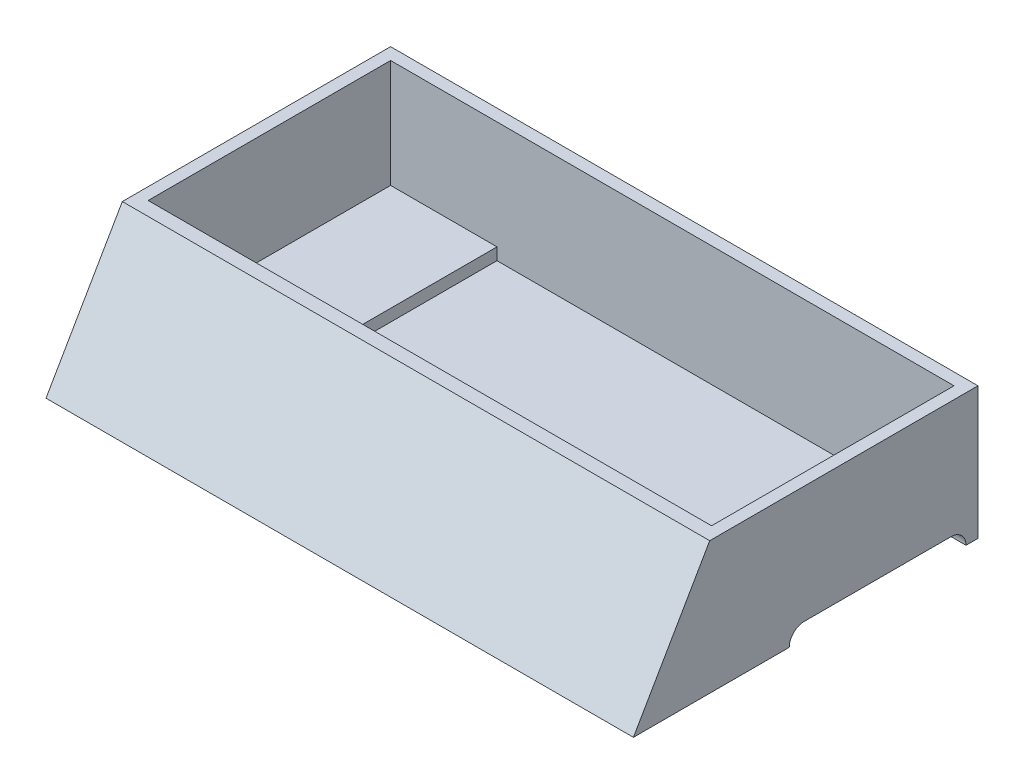
SolidWorks part; units mm, degrees
ref_plane "Alzado" through (0, 0, 0) normal (0, 0, 1) x (1, 0, 0)
ref_plane "Planta" through (0, 0, 0) normal (0, 1, 0) x (1, 0, 0)
ref_plane "Vista lateral" through (0, 0, 0) normal (1, 0, 0) x (0, 0, -1)
sketch "Croquis1" plane through (0, 0, 0) normal (1, 0, 0) x (0, 0, -1)
  line L0 (0, 0) -> (114.98, 0)
  line L1 (114.98, 0) -> (114.98, 44.1)
  line L2 (114.98, 44.1) -> (25.4611, 44.1)
  line L3 (0, 0) -> (25.4611, 44.1)
  line L4 (114.9845, -5.19) -> (114.9845, 15.0485) construction
  dimension "D1" = 114.98
  dimension "D2" = 44.1
  dimension "D3" = 120
extrude "Saliente-Extruir1" add sketch "Croquis1" along normal blind 196
shell "Vaciado1" thickness 4 removed face at (98, 44.1, -70.2206)
sketch "Croquis2" plane through (0, 0, 0) normal (0, -1, 0) x (-1, 0, 0)
  line L0 (-196, 114.98) -> (0, 114.98) construction
  line L1 (-37.5, 51.9947) -> (0, 51.9947)
  line L2 (-37.5, 51.9947) -> (-37.5, 110.98)
  line L3 (-37.5, 110.98) -> (0, 110.98)
  line L4 (0, 51.9947) -> (0, 110.98)
  line L5 (-37.5, 51.9947) -> (0, 110.98) construction
  line L6 (-37.5, 110.98) -> (0, 51.9947) construction
  line L7 (-196, 110.98) -> (-158.5, 110.98)
  line L8 (-196, 110.98) -> (-196, 51.9947)
  line L9 (-196, 51.9947) -> (-158.5, 51.9947)
  line L10 (-158.5, 110.98) -> (-158.5, 51.9947)
  line L11 (-196, 110.98) -> (-158.5, 51.9947) construction
  line L12 (-196, 51.9947) -> (-158.5, 110.98) construction
  point P4 (-18.75, 81.4873)
  point P11 (-177.25, 81.4873)
  dimension "D1" = 4
  dimension "D2" = 4
extrude "Cortar-Extruir1" cut sketch "Croquis2" against normal blind 5
ref_plane "Plano1" through (0, 5, 0) normal (0, 1, 0) x (1, 0, 0)
sketch "Croquis3" plane through (0, 5, 0) normal (0, 1, 0) x (1, 0, 0)
  line L0 (158.5, 51.9947) -> (192, 51.9947) construction
  line L1 (156.5, 49.9947) -> (192, 49.9947)
  line L2 (156.5, 49.9947) -> (156.5, 110.98)
  line L3 (156.5, 110.98) -> (192, 110.98)
  line L4 (192, 49.9947) -> (192, 110.98)
  line L5 (156.5, 49.9947) -> (192, 110.98) construction
  line L6 (156.5, 110.98) -> (192, 49.9947) construction
  line L7 (158.5, 110.98) -> (158.5, 51.9947) construction
  point P4 (174.25, 80.4873)
  dimension "D1" = 2
  dimension "D2" = 2
extrude "Saliente-Extruir2" add sketch "Croquis3" along normal blind 3
sketch "Croquis4" plane through (0, 4, 0) normal (0, 1, 0) x (1, 0, 0)
  line L0 (156.5, 49.9947) -> (192, 49.9947)
  line L1 (192, 49.9947) -> (192, 51.9947)
  line L2 (192, 110.98) -> (192, 30.0799) construction
  line L3 (156.5, 49.9947) -> (156.5, 110.98)
  line L4 (156.5, 110.98) -> (158.5, 110.98)
  line L5 (192, 110.98) -> (4, 110.98) construction
  line L6 (158.5, 110.98) -> (158.5, 51.9947)
  line L7 (158.5, 51.9947) -> (192, 51.9947)
  dimension "D1" = 2
  dimension "D2" = 2
  dimension "D3" = 2
extrude "Saliente-Extruir3" add sketch "Croquis4" along normal blind 3
ref_plane "Plano2" through (98, 0, 0) normal (1, 0, 0) x (0, 0, -1)
mirror "Simetría1" about plane through (98, 0, 0) normal (1, 0, 0) of "Saliente-Extruir3", "Saliente-Extruir2"
fillet "Redondeo1" radius 5 4 edges at (177.25, 5, -51.9947) (177.25, 5, -110.98) (18.75, 5, -110.98) (18.75, 5, -51.9947)
fillet "Redondeo2" radius 5 6 edges at (37.5, 3.5355, -109.5155) (37.5, 3.5355, -53.4591) (158.5, 3.5355, -53.4591) (158.5, 3.5355, -109.5155) (37.5, 5, -81.4873) (158.5, 5, -81.4873)
sketch "Croquis7" plane through (0, 0, 0) normal (0, -1, 0) x (-1, 0, 0)
  line L0 (0, 0) -> (-196, 0) construction
  line L1 (-88, 7.5) -> (-108, 7.5)
  line L2 (-88, 7.5) -> (-88, 10.5)
  line L3 (-88, 10.5) -> (-108, 10.5)
  line L4 (-108, 7.5) -> (-108, 10.5)
  line L5 (-88, 7.5) -> (-108, 10.5) construction
  line L6 (-88, 10.5) -> (-108, 7.5) construction
  line L7 (-98, 0) -> (-98, 53.5164) construction
  point P4 (-98, 9)
  dimension "D1" = 20
  dimension "D2" = 3
  dimension "D3" = 10
  dimension "D4" = 15
extrude "Cortar-Extruir2" cut sketch "Croquis7" against normal up to next
